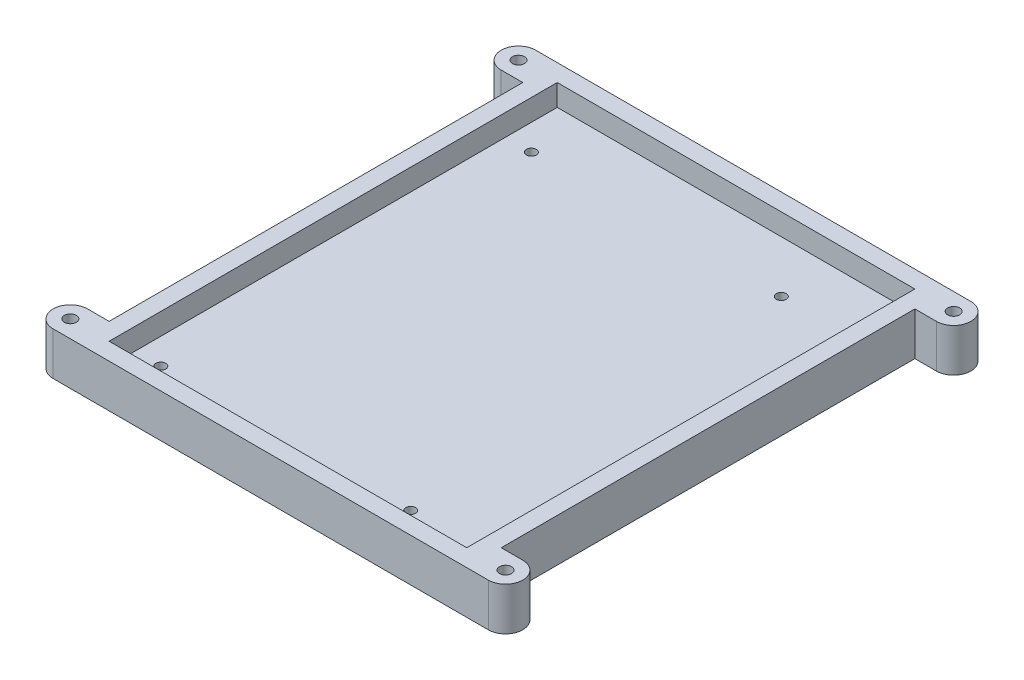
SolidWorks part; units mm, degrees
ref_plane "Front Plane" through (0, 0, 0) normal (0, 0, 1) x (1, 0, 0)
ref_plane "Top Plane" through (0, 0, 0) normal (0, 1, 0) x (1, 0, 0)
ref_plane "Right Plane" through (0, 0, 0) normal (1, 0, 0) x (0, 0, -1)
sketch "Sketch1" plane through (0, 0, 0) normal (0, 1, 0) x (1, 0, 0)
  line L0 (0, 56) -> (0, -56) construction
  line L1 (-39.5, 50) -> (39.5, 50) construction
  line L2 (-39.5, 50) -> (-39.5, -50) construction
  line L3 (-39.5, -50) -> (39.5, -50) construction
  line L4 (39.5, 50) -> (39.5, -50) construction
  line L5 (-45.5, 56) -> (45.5, 56)
  line L6 (-45.5, 56) -> (-45.5, -56)
  line L7 (-45.5, -56) -> (45.5, -56)
  line L8 (45.5, 56) -> (45.5, -56)
  circle A0 centre (-35.5, -46) radius 1.15
  circle A1 centre (22.5, -46) radius 1.15
  circle A2 centre (22.5, 40) radius 1.15
  circle A3 centre (-35.5, 40) radius 1.15
  point P4 (-39.5, 0)
  point P6 (0, 50)
  point P21 (0, 0)
  point P22 (0, 0)
  point P23 (0, 0)
  point P24 (0, 0)
  point P25 (-28.5, -45.728)
  dimension "D5" = 2.3
  dimension "D6" = 86
  dimension "D7" = 58
  dimension "D8" = 4
  dimension "D9" = 4
  dimension "D1" = 79
  dimension "D2" = 100
  dimension "D3" = 112
  dimension "D4" = 91
extrude "Base" add sketch "Sketch1" along normal blind 10
sketch "Sketch2" plane through (0, 10, 0) normal (0, 1, 0) x (1, 0, 0)
  line L0 (0, 52) -> (0, -52) construction
  line L1 (-41.5, 52) -> (41.5, 52)
  line L2 (-41.5, 52) -> (-41.5, -52)
  line L3 (-41.5, -52) -> (41.5, -52)
  line L4 (41.5, 52) -> (41.5, -52)
  line L5 (-45.5, -56) -> (45.5, -56) construction
  line L6 (-45.5, 56) -> (-45.5, -56) construction
  dimension "D1" = 4
  dimension "D2" = 4
extrude "Module Cutout" cut sketch "Sketch2" against normal blind 5
sketch "Sketch3" plane through (0, 10, 0) normal (0, 1, 0) x (1, 0, 0)
  line L0 (-45.5, 56) -> (-50.5, 56)
  line L1 (-45.5, 56) -> (-45.5, -56) construction
  line L2 (-45.5, 56) -> (-45.5, 48)
  line L3 (-45.5, 48) -> (-50.5, 48)
  line L4 (45.5, 56) -> (-45.5, 56) construction
  line L5 (0, 56) -> (0, -56) construction
  line L6 (-45.5, -56) -> (45.5, -56) construction
  line L7 (45.5, 48) -> (50.5, 48)
  line L8 (45.5, 56) -> (45.5, 48)
  line L9 (45.5, 56) -> (50.5, 56)
  line L10 (-45.5, 0) -> (45.5, 0) construction
  line L11 (45.5, -56) -> (45.5, 56) construction
  line L12 (45.5, -56) -> (50.5, -56)
  line L13 (45.5, -56) -> (45.5, -48)
  line L14 (45.5, -48) -> (50.5, -48)
  line L15 (-45.5, -48) -> (-50.5, -48)
  line L16 (-45.5, -56) -> (-45.5, -48)
  line L17 (-45.5, -56) -> (-50.5, -56)
  arc A0 (-50.5, 48) -> (-50.5, 56) centre (-50.5, 52) cw
  circle A1 centre (-50.5, 52) radius 1.4
  circle A2 centre (50.5, 52) radius 1.4
  arc A3 (50.5, 48) -> (50.5, 56) centre (50.5, 52) ccw
  arc A4 (50.5, -48) -> (50.5, -56) centre (50.5, -52) cw
  circle A5 centre (50.5, -52) radius 1.4
  circle A6 centre (-50.5, -52) radius 1.4
  arc A7 (-50.5, -48) -> (-50.5, -56) centre (-50.5, -52) ccw
  dimension "D1" = 2.8
  dimension "D2" = 8
  dimension "D3" = 5
extrude "Case Assembly Holes" add sketch "Sketch3" against normal up to surface (10 mm away) up to face at (0, 0, 0)
